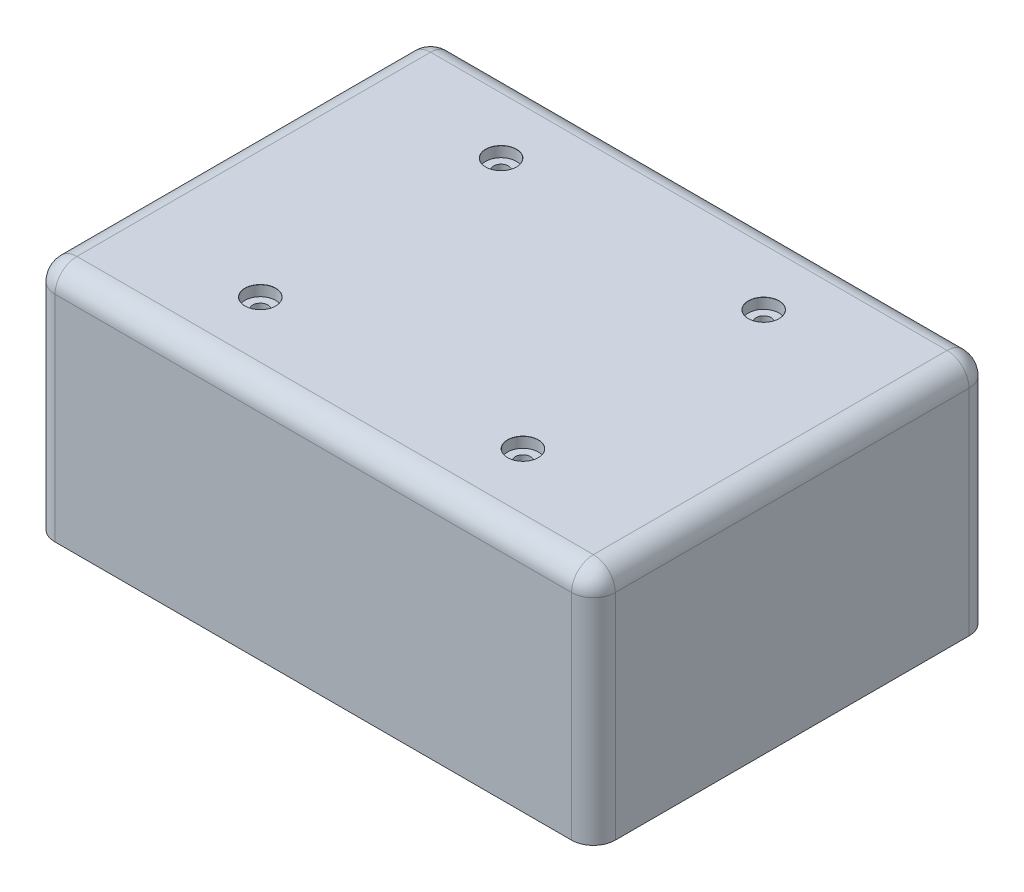
SolidWorks part; units mm, degrees
ref_plane "Front Plane" through (0, 0, 0) normal (0, 0, 1) x (1, 0, 0)
ref_plane "Top Plane" through (0, 0, 0) normal (0, 1, 0) x (1, 0, 0)
ref_plane "Right Plane" through (0, 0, 0) normal (1, 0, 0) x (0, 0, -1)
sketch "Sketch1" plane through (0, 0, 0) normal (0, 1, 0) x (1, 0, 0)
  line L1 (-64, -45.4) -> (64, -45.4)
  line L2 (-64, -45.4) -> (-64, 45.4)
  line L3 (-64, 45.4) -> (64, 45.4)
  line L4 (64, -45.4) -> (64, 45.4)
  line L5 (-64, -45.4) -> (64, 45.4) construction
  line L6 (-64, 45.4) -> (64, -45.4) construction
  point P0 (0, 0)
  dimension "D1" = 128
  dimension "D2" = 90.8
extrude "Boss-Extrude1" add sketch "Sketch1" along normal blind 4
sketch "Sketch2" plane through (0, 4, 0) normal (0, 1, 0) x (1, 0, 0)
  line L0 (-30, 27.5) -> (30, 27.5) construction
  line L1 (30, 27.5) -> (30, -27.5) construction
  line L2 (30, -27.5) -> (-30, -27.5) construction
  line L3 (-30, -27.5) -> (-30, 27.5) construction
  point P0 (30, 27.5)
  point P1 (-30, 27.5)
  point P2 (-30, -27.5)
  point P3 (30, -27.5)
  point P6 (-30, 0)
  point P9 (0, 27.5)
  dimension "D1" = 60
  dimension "D2" = 55
hole_wizard "CBORE for M3 Pan Head Machine Screw1" positions "Sketch3" profile "Sketch4" counterbore size "M3" standard "ANSI Metric" end condition through all
sketch "Sketch3" plane through (0, 4, 0) normal (0, 1, 0) x (1, 0, 0)
  point P0 (-30, 27.5)
  point P3 (30, 27.5)
  point P6 (-30, -27.5)
  point P9 (30, -27.5)
sketch "Sketch4" plane through (-30, 4, -27.5) normal (1, 0, 0) x (0, 0, 1)
  line L0 (0, 0) -> (0, 4)
  line L1 (0, 4) -> (1.7, 4)
  line L3 (1.7, 4) -> (1.7, 2.4)
  line L4 (3.5, 2.4) -> (1.7, 2.4)
  line L5 (3.5, 2.4) -> (3.5, 0.025)
  line L6 (3.5, 0.025) -> (3.525, 0)
  line L7 (3.525, 0) -> (0, 0)
  line L8 (-3.5, 0.025) -> (-3.525, 0) construction
  line L11 (0, -6.35) -> (0, 107.95) construction
  dimension "Thru Hole Dia." = 3.4
  dimension "Thru Hole Depth" = 4
  dimension "C'Bore Dia." = 7
  dimension "C'Bore Depth" = 2.4
  dimension "Near C'Sink Dia." = 7.05
  dimension "Near C'Sink Angle" = 90
sketch "Sketch5" plane through (0, 0, 0) normal (0, -1, 0) x (1, 0, 0)
  line L0 (-59, 35.4) -> (59, 35.4)
  line L1 (59, 35.4) -> (59, -35.4)
  line L2 (59, -35.4) -> (-59, -35.4)
  line L3 (-59, -35.4) -> (-59, 35.4)
  line L8 (-64, 45.4) -> (64, 45.4)
  line L9 (64, 45.4) -> (64, -45.4)
  line L10 (64, -45.4) -> (-64, -45.4)
  line L11 (-64, -45.4) -> (-64, 45.4)
  dimension "D1" = 10
  dimension "D2" = 10
  dimension "D3" = 5
  dimension "D4" = 5
extrude "Boss-Extrude2" add sketch "Sketch5" along normal blind 50
fillet "Fillet1" radius 5 12 edges at (-64, -23, -45.4) (64, 4, 0) (0, 4, -45.4) (0, 4, 45.4) (-64, 4, 0) (-64, -23, 45.4) (64, -23, 45.4) (64, -23, -45.4) (-59, -25, -35.4) (59, -25, -35.4) (59, -25, 35.4) (-59, -25, 35.4)
sketch "Sketch7" plane through (0, -50, 0) normal (0, -1, 0) x (1, 0, 0)
  line L0 (-44, 40.4) -> (44, 40.4) construction
  line L1 (44, 40.4) -> (44, -40.4) construction
  line L2 (44, -40.4) -> (-44, -40.4) construction
  line L3 (-44, -40.4) -> (-44, 40.4) construction
  line L4 (-64, 40.4) -> (-64, -40.4) construction
  line L5 (64, -40.4) -> (64, 40.4) construction
  line L6 (-50.2088, 45.4) -> (-50.2088, 35.4) construction
  line L7 (59, 45.4) -> (-59, 45.4) construction
  line L8 (54, 35.4) -> (-54, 35.4) construction
  line L9 (-50.2088, -35.4) -> (-50.2088, -45.4) construction
  line L10 (-54, -35.4) -> (54, -35.4) construction
  line L11 (-59, -45.4) -> (59, -45.4) construction
  point P0 (-44, -40.4)
  point P1 (44, -40.4)
  point P2 (44, 40.4)
  point P3 (-44, 40.4)
  point P18 (-50.2088, 40.4)
  point P25 (0, 0)
  point P26 (-50.2088, -40.4)
  dimension "D1" = 20
  dimension "D2" = 20
hole_wizard "Hole1" positions "Sketch8" profile "Sketch9" legacy
sketch "Sketch8" plane through (0, -50, 0) normal (0, -1, 0) x (-1, 0, 0)
  point P0 (-44, 40.4)
  point P3 (44, 40.4)
  point P6 (44, -40.4)
  point P9 (-44, -40.4)
sketch "Sketch9" plane through (44, -50, -40.4) normal (1, 0, 0) x (0, 0, -1)
  line L0 (0, 0) -> (0, 8)
  line L1 (0, 8) -> (2.4, 8)
  line L2 (2.4, 8) -> (2.4, 6)
  line L3 (2.4, 6) -> (2.7, 6)
  line L4 (2.7, 6) -> (2.7, 0)
  line L5 (2.7, 0) -> (0, 0)
  line L6 (0, 110) -> (0, -10) construction
  dimension "Diameter" = 4.8
  dimension "Depth" = 8
  dimension "C-Bore Diameter" = 5.4
  dimension "C-Bore Depth" = 6
chamfer "Chamfer1" distance 6 distance2 0.3 4 edges at (-44, -44, 37.7) (-44, -44, -43.1) (44, -44, -43.1) (44, -44, 37.7) first distance on face at (-44, -44, 37.7) first distance on face at (-44, -44, -43.1) first distance on face at (44, -44, -43.1) first distance on face at (44, -44, 37.7)
sketch "Sketch10" plane through (-64, 0, 0) normal (-1, 0, 0) x (0, 0, 1)
  line L0 (40.4, -1) -> (-40.4, -1) construction
  line L1 (-15, -1) -> (15, -1)
  line L2 (-15, -1) -> (-15, -16)
  line L3 (-15, -16) -> (15, -16)
  line L4 (15, -1) -> (15, -16)
  point P6 (0, -16)
  dimension "D1" = 15
  dimension "D2" = 30
extrude "Cut-Extrude1" cut sketch "Sketch10" against normal up to next
